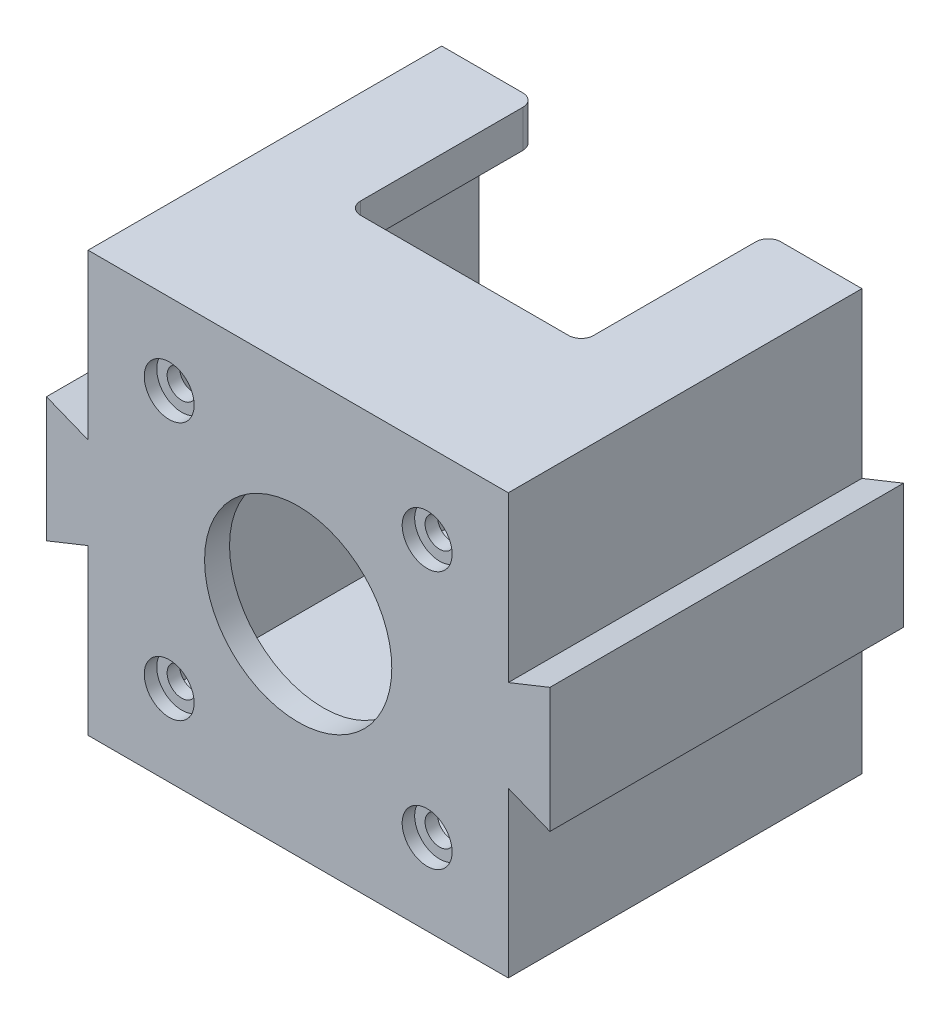
SolidWorks part; units mm, degrees
ref_plane "Front Plane" through (0, 0, 0) normal (0, 0, 1) x (1, 0, 0)
ref_plane "Top Plane" through (0, 0, 0) normal (0, 1, 0) x (1, 0, 0)
ref_plane "Right Plane" through (0, 0, 0) normal (1, 0, 0) x (0, 0, -1)
sketch "Sketch1" plane through (0, 0, 0) normal (0, 0, 1) x (1, 0, 0)
  line L0 (-15.5, 15.5) -> (15.5, 15.5) construction
  line L1 (-21.25, -21.25) -> (21.25, -21.25)
  line L2 (-21.25, -21.25) -> (-21.25, 21.25)
  line L3 (-21.25, 21.25) -> (21.25, 21.25)
  line L4 (21.25, -21.25) -> (21.25, 21.25)
  line L5 (-21.25, -21.25) -> (21.25, 21.25) construction
  line L6 (-21.25, 21.25) -> (21.25, -21.25) construction
  line L7 (-25.25, 25.25) -> (25.25, 25.25)
  line L8 (-25.25, 25.25) -> (-25.25, -25.25)
  line L9 (-25.25, -25.25) -> (25.25, -25.25)
  line L10 (25.25, 25.25) -> (25.25, -25.25)
  line L11 (-25.25, 25.25) -> (25.25, -25.25) construction
  line L12 (-25.25, -25.25) -> (25.25, 25.25) construction
  circle A5 centre (0, 0) radius 11.25
  circle A6 centre (-15.5, 15.5) radius 1.75
  circle A7 centre (15.5, 15.5) radius 1.75
  circle A8 centre (-15.5, -15.5) radius 1.75
  circle A9 centre (15.5, -15.5) radius 1.75
  point P0 (0, 0)
  dimension "D5" = 22.5
  dimension "D6" = 3.5
  dimension "D7" = 31
  dimension "D1" = 42.5
  dimension "D2" = 42.5
  dimension "D3" = 4
  dimension "D4" = 4
  dimension "D8" = 2
  dimension "D9" = 31
extrude "Boss-Extrude1" add sketch "Sketch1" along normal blind 3 contours L1 L4 L3 L2 A5 A9 A7 | L10 L7 L8 L9 L4 L1 L2 L3 region at (-20.649, 0, 0) region at (0, 24.5358, 0)
extrude "Boss-Extrude2" add sketch "Sketch1<4>" against normal blind 39.5 contours L10 L7 L8 L9 L4 L1 L2 L3 region at (0, 24.5358, 0)
sketch "Sketch1<4>" plane through (0, 0, 0) normal (0, 0, 1) x (1, 0, 0) same geometry as "Sketch1"
sketch "Sketch6" plane through (0, 0, 0) normal (0, 0, -1) x (-1, 0, 0)
  line L0 (-21.25, -21.25) -> (-21.25, 21.25) construction
  line L1 (-20.75, -20.75) -> (20.75, -20.75)
  line L2 (-20.75, -20.75) -> (-20.75, 20.75)
  line L3 (-20.75, 20.75) -> (20.75, 20.75)
  line L4 (20.75, -20.75) -> (20.75, 20.75)
  line L5 (-20.75, -20.75) -> (20.75, 20.75) construction
  line L6 (-20.75, 20.75) -> (20.75, -20.75) construction
  line L7 (21.25, -21.25) -> (-21.25, -21.25) construction
  point P0 (0, 0)
  line M8 (-21.25, 21.25) -> (-21.25, -21.25)
  line M9 (-21.25, -21.25) -> (21.25, -21.25)
  line M10 (21.25, -21.25) -> (21.25, 21.25)
  line M11 (21.25, 21.25) -> (-21.25, 21.25)
  dimension "D1" = 0.5
  dimension "D2" = 0.5
extrude "Boss-Extrude4" add sketch "Sketch6" along normal up to surface (39.5 mm away) contours L4 L1 L2 L3 M11 M8 M9 M10 region at (0, 21.1899, 0) up to face at (0, 0, -39.5)
sketch "Sketch2" plane through (0, 25.25, 0) normal (0, 1, 0) x (1, 0, 0)
  line L0 (-25.25, 39.5) -> (25.25, 39.5) construction
  line L1 (-14, 39.5) -> (14, 39.5)
  line L2 (-14, 39.5) -> (-14, 18.5)
  line L3 (-12.5, 17) -> (12.5, 17)
  line L4 (14, 39.5) -> (14, 18.5)
  line L5 (-25.25, -3) -> (25.25, -3) construction
  line L6 (-14, 17) -> (-25.25, 39.5) construction
  line L7 (14, 17) -> (25.25, 39.5) construction
  arc A0 (12.5, 17) -> (14, 18.5) centre (12.5, 18.5) ccw
  arc A1 (-14, 18.5) -> (-12.5, 17) centre (-12.5, 18.5) ccw
  dimension "D3" = 1.5
  dimension "D1" = 20
  dimension "D2" = 28
extrude "Cut-Extrude1" cut sketch "Sketch2" against normal blind 20
fillet "Fillet1" radius 1.5 2 edges at (14, 23, -39.5) (-14, 23, -39.5)
sketch "Sketch4" plane through (0, 0, 3) normal (0, 0, 1) x (1, 0, 0)
  circle A0 centre (15.5, 15.5) radius 3
  circle A3 centre (15.5, -15.5) radius 3
  circle A4 centre (-15.5, 15.5) radius 3
  circle A5 centre (-15.5, -15.5) radius 3
  dimension "D1" = 6
extrude "Cut-Extrude2" cut sketch "Sketch4" against normal blind 1.5
sketch "Sketch5" plane through (0, 0, 3) normal (0, 0, 1) x (1, 0, 0)
  line L0 (25.25, 5.5) -> (30.25, 7.5)
  line L1 (25.25, 25.25) -> (25.25, -25.25) construction
  line L2 (30.25, 7.5) -> (30.25, -7.5)
  line L3 (30.25, -7.5) -> (25.25, -5.5)
  line L4 (25.25, -5.5) -> (25.25, 5.5)
  line L5 (25.25, 25.25) -> (30.25, 7.5) construction
  line L6 (30.25, -7.5) -> (25.25, -25.25) construction
  line L7 (0, 25.25) -> (0, -25.25) construction
  line L8 (-25.25, 25.25) -> (25.25, 25.25) construction
  line L9 (-25.25, -25.25) -> (25.25, -25.25) construction
  line L10 (-30.25, -7.5) -> (-25.25, -5.5)
  line L11 (-30.25, 7.5) -> (-30.25, -7.5)
  line L12 (-25.25, 5.5) -> (-30.25, 7.5)
  line L13 (-25.25, -5.5) -> (-25.25, 5.5)
  dimension "D1" = 15
  dimension "D2" = 2
  dimension "D3" = 5
extrude "Boss-Extrude3" add sketch "Sketch5" against normal up to surface (42.5 mm away) up to face at (0, 7.6667, -39.5)
